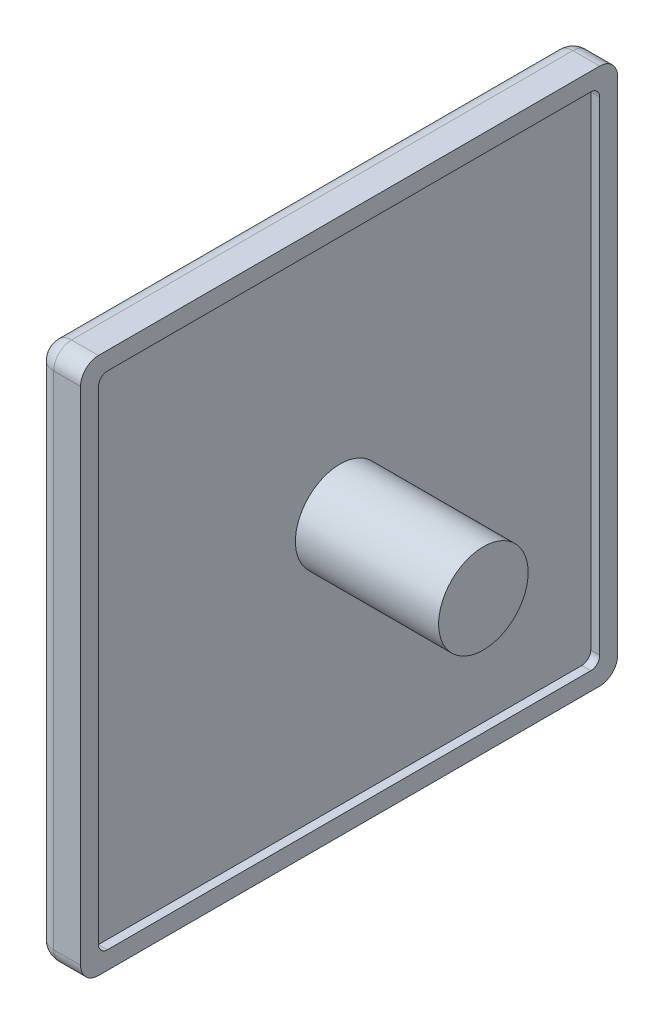
SolidWorks part; units mm, degrees
material "PVC Rigid"
ref_plane "Front Plane" through (0, 0, 0) normal (0, 0, 1) x (1, 0, 0)
ref_plane "Top Plane" through (0, 0, 0) normal (0, 1, 0) x (1, 0, 0)
ref_plane "Right Plane" through (0, 0, 0) normal (1, 0, 0) x (0, 0, -1)
sketch "Sketch2" plane through (0, 0, 0) normal (1, 0, 0) x (0, 0, -1)
  line L1 (0, 0) -> (30, 0)
  line L2 (0, 0) -> (0, 30)
  line L3 (0, 30) -> (30, 30)
  line L4 (30, 0) -> (30, 30)
  dimension "D1" = 30
  dimension "D2" = 30
extrude "Boss-Extrude1" add sketch "Sketch2" along normal blind 2.5
sketch "Sketch3" plane through (2.5, 0, 0) normal (1, 0, 0) x (0, 0, -1)
  line L0 (0, 30) -> (0, 0) construction
  line L1 (1, 29) -> (29, 29)
  line L2 (1, 29) -> (1, 1)
  line L3 (1, 1) -> (29, 1)
  line L4 (29, 29) -> (29, 1)
  line L5 (30, 30) -> (0, 30) construction
  line L6 (30, 0) -> (30, 30) construction
  line L7 (0, 0) -> (30, 0) construction
  dimension "D1" = 1
  dimension "D2" = 1
  dimension "D3" = 1
  dimension "D4" = 1
extrude "Cut-Extrude1" cut sketch "Sketch3" against normal blind 0.5
fillet "Fillet1" radius 1 4 edges at (0, 0, -15) (0, 15, -30) (0, 30, -15) (0, 15, 0)
fillet "Fillet2" radius 1 8 edges at (0.2929, 29.7071, -0.2929) (0.2929, 29.7071, -29.7071) (0.2929, 0.2929, -29.7071) (0.2929, 0.2929, -0.2929) (1.75, 30, 0) (1.75, 30, -30) (1.75, 0, -30) (1.75, 0, 0)
fillet "Fillet3" radius 0.5 4 edges at (2.25, 1, -29) (2.25, 29, -29) (2.25, 29, -1) (2.25, 1, -1)
sketch "Sketch4" plane through (2, 0, 0) normal (1, 0, 0) x (0, 0, -1)
sketch "Sketch5" plane through (2, 0, 0) normal (1, 0, 0) x (0, 0, -1)
  line L0 (28.5, 29) -> (1.5, 29) construction
  line L1 (29, 1.5) -> (29, 28.5) construction
  circle A1 centre (15, 15) radius 2.5
  point P4 (15, 29)
  point P7 (29, 15)
  dimension "D1" = 5
extrude "Boss-Extrude2" add sketch "Sketch5" along normal blind 8
